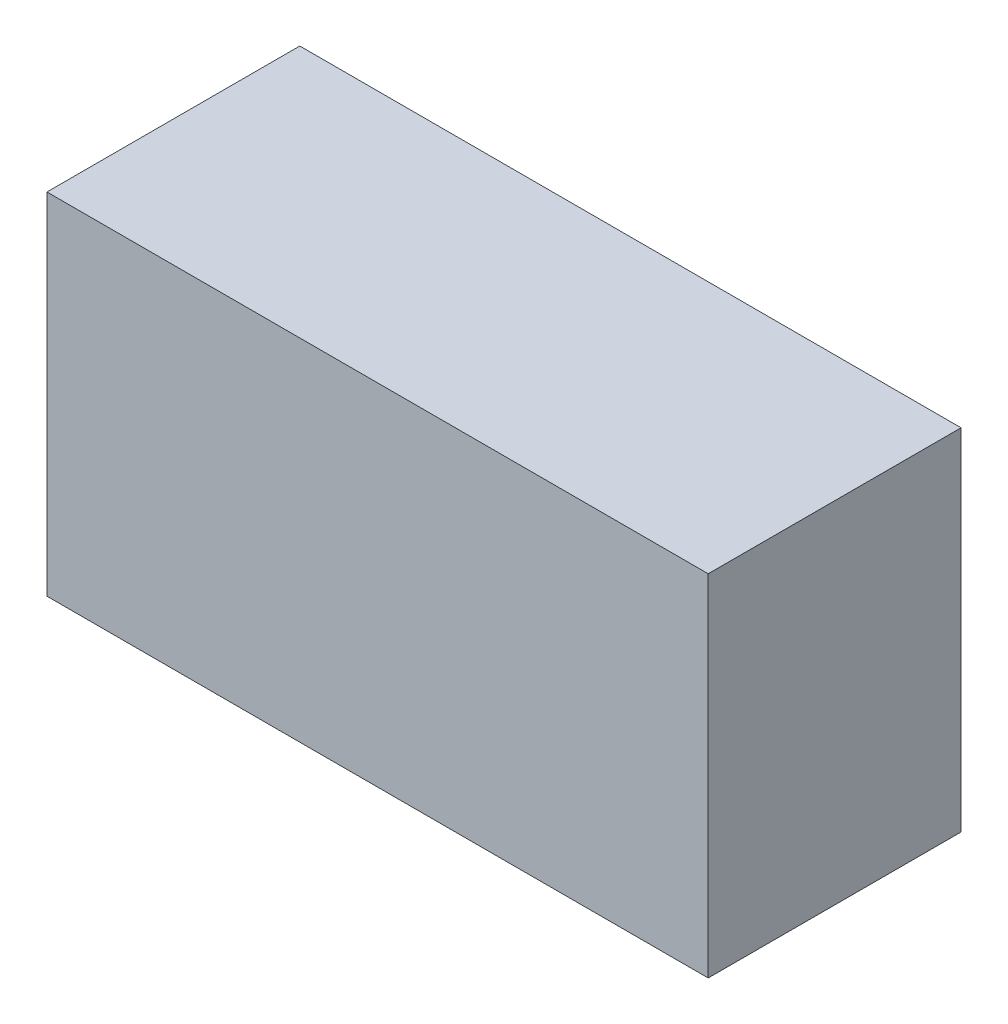
SolidWorks part; units mm, degrees
ref_plane "Front Plane" through (0, 0, 0) normal (0, 0, 1) x (1, 0, 0)
ref_plane "Top Plane" through (0, 0, 0) normal (0, 1, 0) x (1, 0, 0)
ref_plane "Right Plane" through (0, 0, 0) normal (1, 0, 0) x (0, 0, -1)
sketch "Sketch1" plane through (0, 0, 0) normal (0, 0, 1) x (1, 0, 0)
  line L1 (-25.5, -13.5) -> (25.5, -13.5)
  line L2 (-25.5, -13.5) -> (-25.5, 13.5)
  line L3 (-25.5, 13.5) -> (25.5, 13.5)
  line L4 (25.5, -13.5) -> (25.5, 13.5)
  line L5 (-25.5, -13.5) -> (25.5, 13.5) construction
  line L6 (-25.5, 13.5) -> (25.5, -13.5) construction
extrude "Envelope" add sketch "Sketch1" along normal blind 19.5
